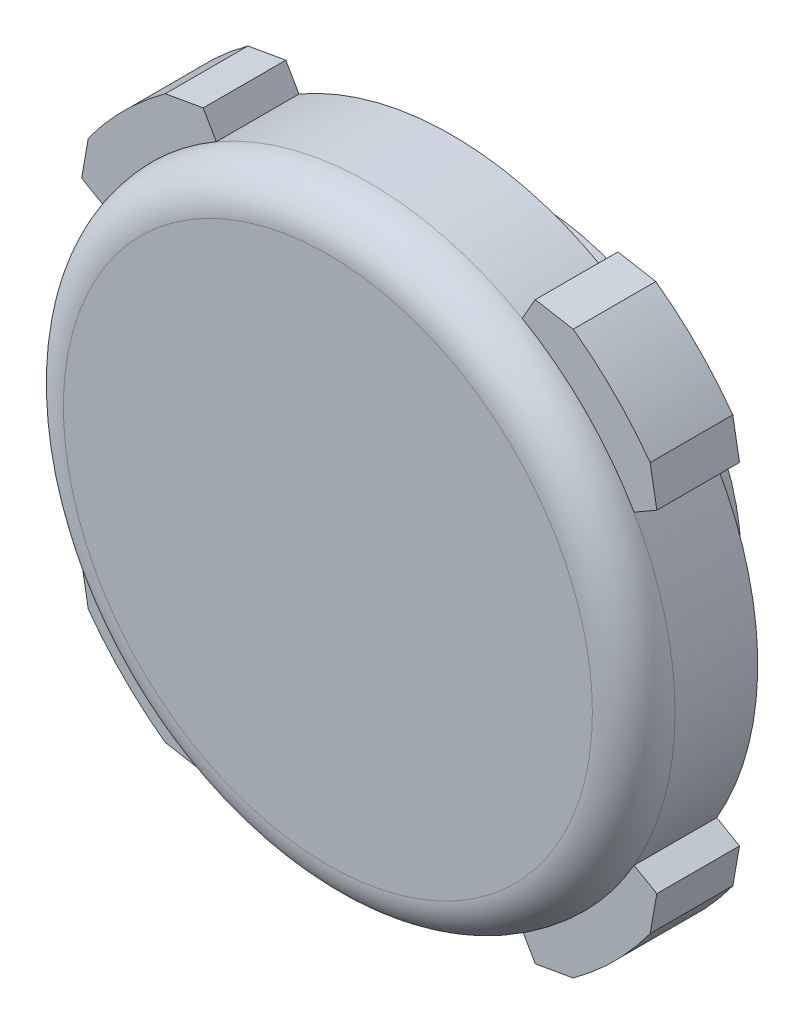
SolidWorks part; units mm, degrees
ref_plane "前基準面" through (0, 0, 0) normal (0, 0, 1) x (1, 0, 0)
ref_plane "上基準面" through (0, 0, 0) normal (0, 1, 0) x (1, 0, 0)
ref_plane "右基準面" through (0, 0, 0) normal (1, 0, 0) x (0, 0, -1)
ref_axis "基準軸1" through (0, -55, 0) along (0, 1, 0)
ref_axis "基準軸2" through (-88.99, 0, 0) along (1, 0, 0)
ref_axis "基準軸3" through (0, 0, 55) along (0, 0, -1)
sketch "草圖1" plane through (0, 0, 0) normal (0, 0, 1) x (1, 0, 0)
  circle A0 centre (0, 0) radius 37
  dimension "D1" = 74
extrude "填料-伸長1" add sketch "草圖1" along normal blind 15
ref_plane "平面1" through (0, 0, 38) normal (0, 0, 1) x (1, 0, 0)
ref_axis "基準軸4" through (-40.7, 0, 38) along (1, 0, 0)
fillet "圓角2" radius 5 1 edges at (37, 0, 15)
sketch "草圖7" plane through (0, 0, 0) normal (0, 0, 1) x (1, 0, 0)
  line L0 (0, 0) -> (39.6923, 68.7491) construction
  line L1 (0, -55) -> (0, 55) construction
  dimension "D1" = 79.3846
  dimension "D2" = 30
sketch "草圖8" plane through (0, 0, 0) normal (0, 0, 1) x (1, 0, 0)
  line L0 (0, 0) -> (39.6923, 68.7491) construction
  line L1 (21, 36.3731) -> (18.5, 32.0429)
  line L2 (36.3731, 21) -> (32.0429, 18.5)
  line L3 (-88.99, 0) -> (88.99, 0) construction
  arc A0 (32.0429, 18.5) -> (18.5, 32.0429) centre (0, 0) ccw
  arc A1 (36.3731, 21) -> (21, 36.3731) centre (0, 0) ccw
  dimension "D1" = 37
  dimension "D2" = 42
  dimension "D3" = 30
  dimension "D4" = 30
  dimension "D5" = 60
extrude "填料-伸長3" add sketch "草圖8" along normal blind 10
chamfer "導角2" distance 5 angle 20 1 edges at (21, 36.3731, 5) first distance on face at (29.1925, 29.1925, 5)
chamfer "導角3" distance 5 angle 20 1 edges at (36.3731, 21, 5) first distance on face at (30.8646, 27.8022, 5)
pattern_circular "環狀複製排列4" count 4 over 360 about axis through (0, 0, 55) along (0, 0, -1) of "填料-伸長3", "導角2", "導角3"
sketch "草圖9" plane through (0, 0, 0) normal (0, 0, -1) x (-1, 0, 0)
  circle A0 centre (0, 0) radius 25
  circle A1 centre (0, 0) radius 32.5
  circle A2 centre (0, 0) radius 31
  dimension "D1" = 50
  dimension "D2" = 65
  dimension "D3" = 62
extrude "填料-伸長5" add sketch "草圖9" along normal blind 10 contours A0 region at (0, 0, 0)
ref_plane "平面2" through (0, 37, 0) normal (0, 1, 0) x (1, 0, 0)
ref_plane "平面3" through (0, 57, 0) normal (0, 1, 0) x (1, 0, 0)
sketch "草圖10" plane through (0, 0, 0) normal (0, 0, -1) x (-1, 0, 0)
  circle A1 centre (0, 0) radius 25 construction
  circle A2 centre (0, 0) radius 23
  circle A3 centre (0, 0) radius 23
  circle A4 centre (0, 0) radius 25
  dimension "D1" = 2
extrude "除料-伸長1" cut sketch "草圖10" along normal blind 3
